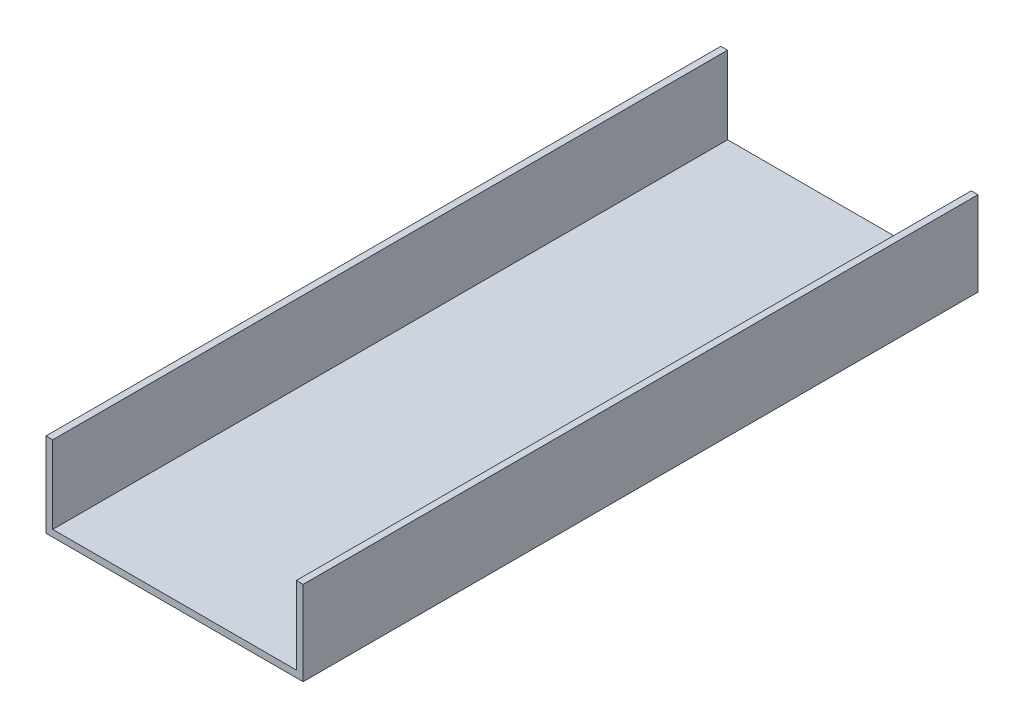
SolidWorks part; units mm, degrees
ref_plane "Alzado" through (0, 0, 0) normal (0, 0, 1) x (1, 0, 0)
ref_plane "Planta" through (0, 0, 0) normal (0, 1, 0) x (1, 0, 0)
ref_plane "Vista lateral" through (0, 0, 0) normal (1, 0, 0) x (0, 0, -1)
sketch "Croquis1" plane through (0, 0, 0) normal (0, 0, 1) x (1, 0, 0)
  line L0 (0, 22.9641) -> (0, -26.2672) construction
  line L1 (-38.1, -12.5) -> (38.1, -12.5) construction
  line L2 (-38.1, -12.5) -> (-38.1, 12.5) construction
  line L3 (-38.1, 12.5) -> (38.1, 12.5) construction
  line L4 (38.1, -12.5) -> (38.1, 12.5) construction
  line L5 (-38.1, -12.5) -> (38.1, 12.5) construction
  line L6 (-38.1, 12.5) -> (38.1, -12.5) construction
  line L7 (-38.1, 12.5) -> (-38.1, -12.5)
  line L8 (-38.1, -12.5) -> (38.1, -12.5)
  line L9 (0, -12.5) -> (0, -10.5)
  line L10 (36.1, -10.5) -> (-36.1, -10.5)
  line L11 (-36.1, -10.5) -> (-36.1, 12.5)
  line L12 (-36.1, 12.5) -> (-38.1, 12.5)
  line L13 (36.1, -10.5) -> (36.1, 12.5)
  line L14 (38.1, 12.5) -> (38.1, -12.5)
  line L15 (36.1, 12.5) -> (38.1, 12.5)
  point P0 (0, 0)
  dimension "D1" = 25
  dimension "D2" = 76.2
  dimension "D3" = 2
  dimension "D4" = 2
extrude "Saliente-Extruir1" add sketch "Croquis1" along normal mid plane 200 contours L11 L12 L7 L8 L9 L10 | L10 L11 L12 L7 L8 L14 L15 L13 region at (-37.1, 12.0443, 0)
